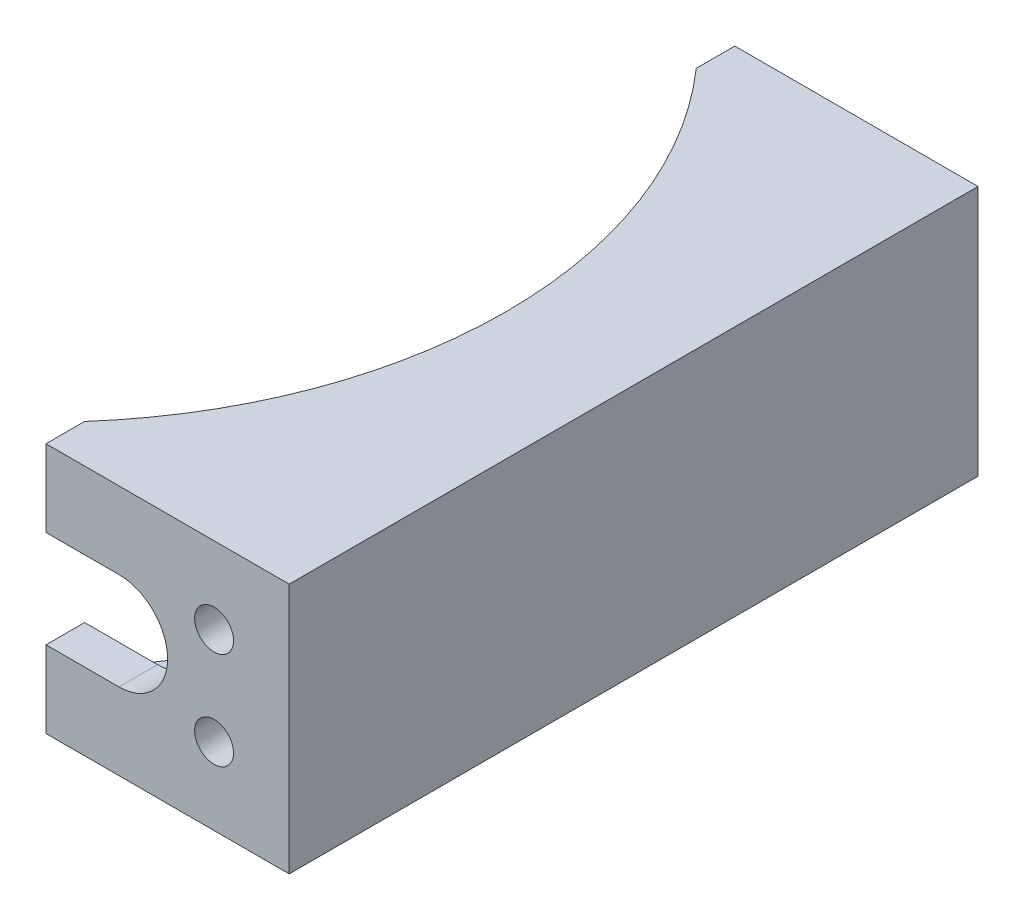
SolidWorks part; units mm, degrees
ref_plane "Front Plane" through (0, 0, 0) normal (0, 0, 1) x (1, 0, 0)
ref_plane "Top Plane" through (0, 0, 0) normal (0, 1, 0) x (1, 0, 0)
ref_plane "Right Plane" through (0, 0, 0) normal (1, 0, 0) x (0, 0, -1)
sketch "Sketch1" plane through (0, 0, 0) normal (0, 1, 0) x (1, 0, 0)
  line L0 (0, 0) -> (20, 0)
  line L1 (20, 0) -> (20, -50.3)
  line L2 (20, -50.3) -> (0, -50.3)
  arc A0 (0, -50.3) -> (0, 0) centre (-28.4864, -25.15) ccw
  dimension "D3" = 38
  dimension "D1" = 20
  dimension "D2" = 50.3
extrude "Boss-Extrude1" add sketch "Sketch1" along normal blind 3.175
sketch "Sketch2" plane through (0, 3.175, 0) normal (0, 1, 0) x (1, 0, 0)
  line L0 (0, -50.3) -> (20, -50.3) construction
  line L1 (20, 0) -> (16.825, 0)
  line L2 (20, 0) -> (20, -50.3)
  line L3 (20, -50.3) -> (16.825, -50.3)
  line L4 (16.825, 0) -> (16.825, -50.3)
  dimension "D1" = 3.175
extrude "Boss-Extrude2" add sketch "Sketch2" along normal blind 14.29
ref_plane "Plane1" through (0, 10.32, 0) normal (0, 1, 0) x (1, 0, 0)
mirror "Mirror1" about plane through (0, 10.32, 0) normal (0, 1, 0) of "Boss-Extrude1"
sketch "Sketch3" plane through (0, 0, 0) normal (0, 0, -1) x (-1, 0, 0)
  line L0 (-20, 20.64) -> (0, 20.64) construction
  line L1 (-20, 0) -> (0, 0)
  line L2 (-20, 0) -> (-20, 20.64)
  line L3 (-20, 20.64) -> (0, 20.64)
  line L4 (0, 0) -> (0, 6.32)
  line L5 (-13.825, 6.32) -> (-13.825, 14.32) construction
  line L6 (9.2538, 10.32) -> (-9.2538, 10.32) construction
  line L7 (-16.825, 17.465) -> (-16.825, 3.175) construction
  line L8 (0, 3.175) -> (0, 0) construction
  line L9 (-6, 6.32) -> (0, 6.32)
  line L10 (-6, 14.32) -> (0, 14.32)
  line L11 (0, 14.32) -> (0, 20.64)
  circle A0 centre (-13.825, 6.32) radius 1.6
  circle A1 centre (-13.825, 14.32) radius 1.6
  arc A2 (-6, 14.32) -> (-6, 6.32) centre (-6, 10.32) ccw
  point P11 (-13.825, 10.32)
  dimension "D1" = 3.2
  dimension "D4" = 8
  dimension "D2" = 8
  dimension "D3" = 3
  dimension "D5" = 6
extrude "Boss-Extrude3" add sketch "Sketch3" along normal blind 3.175
ref_plane "Plane2" through (0, 0, 25.15) normal (0, 0, 1) x (1, 0, 0)
mirror "Mirror2" about plane through (0, 0, 25.15) normal (0, 0, 1) of "Boss-Extrude3"
